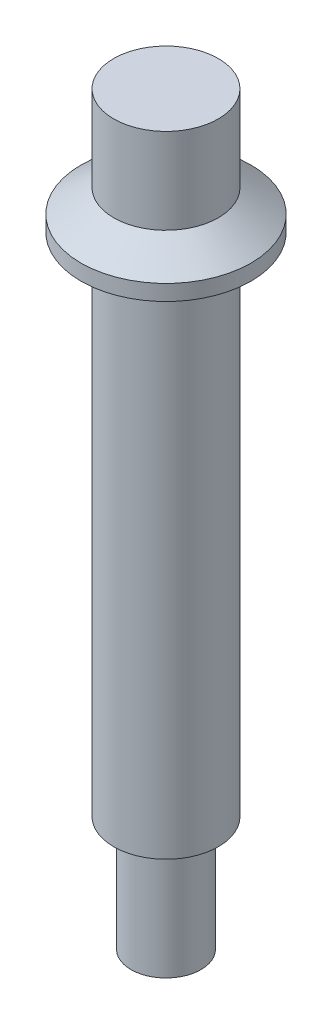
SolidWorks part; units mm, degrees
ref_plane "Front Plane" through (0, 0, 0) normal (0, 0, 1) x (1, 0, 0)
ref_plane "Top Plane" through (0, 0, 0) normal (0, 1, 0) x (1, 0, 0)
ref_plane "Right Plane" through (0, 0, 0) normal (1, 0, 0) x (0, 0, -1)
ref_plane "Plane1" through (0, 0, 0) normal (0, 0, -1) x (-1, 0, 0)
sketch "Sketch1" plane through (0, 0, 0) normal (0, 0, -1) x (-1, 0, 0)
  line L0 (-65, 262.2279) -> (-40, 262.2279)
  line L1 (0, 262.2279) -> (0, 357.2279)
  line L2 (0, 357.2279) -> (-40, 357.2279)
  line L3 (-40, 357.2279) -> (-40, 291.7331)
  line L4 (-40, 291.7331) -> (-65, 274.2279)
  line L5 (-65, 274.2279) -> (-65, 262.2279)
  line L6 (0, 262.2279) -> (0, 357.2279) construction
  line L7 (-40, 262.2279) -> (-40, -124.7721)
  line L8 (-40, -124.7721) -> (-26.75, -124.7721)
  line L9 (-26.75, -124.7721) -> (-26.75, -212.7721)
  line L10 (-26.75, -212.7721) -> (0, -212.7721)
  line L11 (0, -212.7721) -> (0, 262.2279)
  point P8 (-33.375, -124.7721)
  dimension "D1" = 12
  dimension "D2" = 125
  dimension "D3" = 95
  dimension "D4" = 40
  dimension "D5" = 387
  dimension "D6" = 88
  dimension "D7" = 40
  dimension "D8" = 26.75
revolve "Revolve1" add sketch "Sketch1" angle 360 about L6 reverse direction yes
ref_axis "Axis1" through (0, -124.7721, 0) along (0, 1, 0)
hole_wizard "M8x1.0 Tapped Hole1" positions "Sketch3" profile "Sketch4" tap size "M8x1.0" standard "DIN"
sketch "Sketch3" plane through (0, -212.7721, 0) normal (0, -1, 0) x (-1, 0, 0)
  point P0 (0, 16)
  dimension "D1" = 16
sketch "Sketch4" plane through (0, -212.7721, -16) normal (1, 0, 0) x (0, 0, -1)
  line L0 (0, 0) -> (0, 21.103)
  line L1 (0, 21.103) -> (3.5, 19)
  line L2 (3.5, 19) -> (3.5, 0)
  line L5 (3.5, 0) -> (0, 0)
  line L10 (0, 21.103) -> (-3.5, 19) construction
  line L11 (0, -6.35) -> (0, 107.95) construction
  dimension "Tap Drill Dia." = 7
  dimension "Tap Drill Depth" = 19
  dimension "Drill Angle" = 118
cosmetic thread "Hole Thread1" parameters "D1"=16, "D2"=8
pattern_circular "CirPattern1" count 3 every 120 about axis through (0, -124.7721, 0) along (0, 1, 0) of "M8x1.0 Tapped Hole1"
cosmetic thread "Hole Thread2" parameters "D1"=16, "D2"=8
cosmetic thread "Hole Thread3" parameters "D1"=16, "D2"=8
